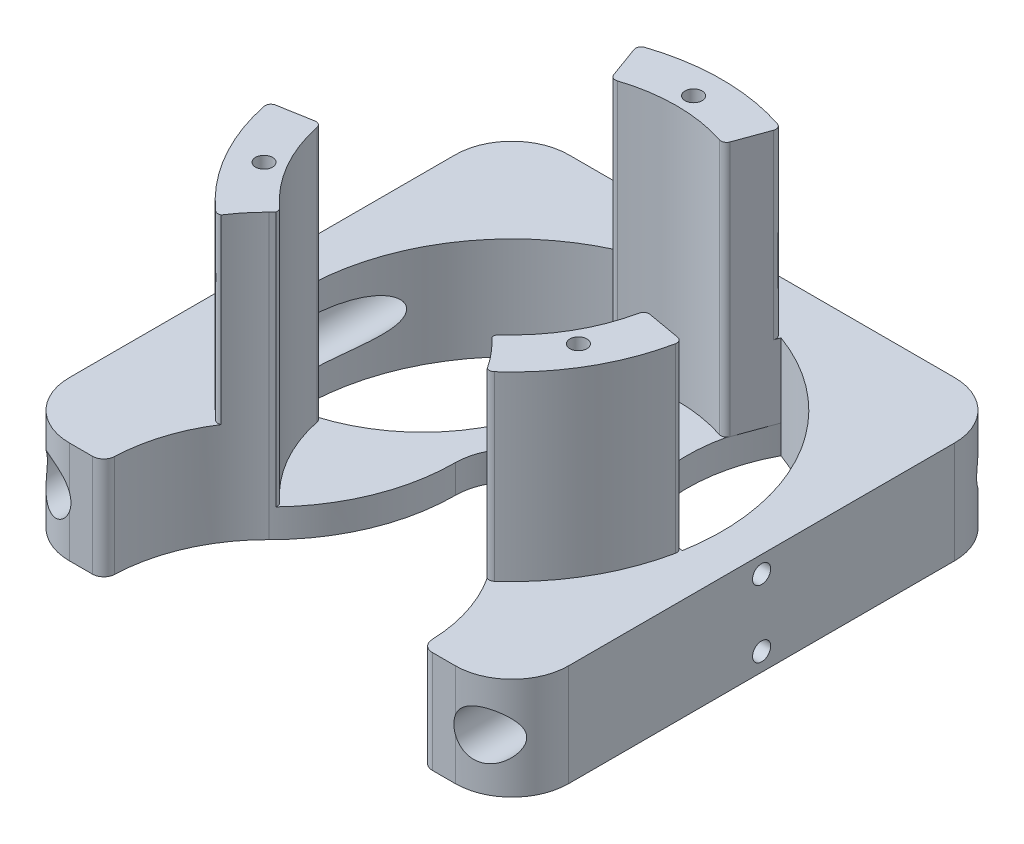
SolidWorks part; units mm, degrees
ref_plane "Front Plane" through (0, 0, 0) normal (0, 0, 1) x (1, 0, 0)
ref_plane "Top Plane" through (0, 0, 0) normal (0, 1, 0) x (1, 0, 0)
ref_plane "Right Plane" through (0, 0, 0) normal (1, 0, 0) x (0, 0, -1)
sketch "Sketch1" plane through (0, 0, 0) normal (0, 1, 0) x (1, 0, 0)
  line L0 (-44, 0) -> (-44, -44) construction
  line L1 (-44, -44) -> (44, -44) construction
  line L2 (44, -44) -> (44, 0) construction
  line L4 (-44, -44) -> (44, -44)
  line L5 (-44, -44) -> (-44, 44)
  line L6 (-44, 44) -> (44, 44)
  line L7 (44, -44) -> (44, 44)
  arc A0 (44, 0) -> (-44, 0) centre (0, 0) ccw construction
  dimension "D1" = 88
extrude "Boss-Extrude1" add sketch "Sketch1" along normal blind 18
sketch "Sketch2" plane through (0, 0, 44) normal (0, 0, 1) x (1, 0, 0)
  line L1 (-1044, 9) -> (48956, 9) construction
  line L2 (0, -1000) -> (0, 49000) construction
  line L3 (-44, 18) -> (-44, 0) construction
  circle A0 centre (-38, 9) radius 4.25
  circle A1 centre (38, 9) radius 4.25
  point P7 (-44, 9)
  dimension "D1" = 8.5
  dimension "D2" = 6
extrude "Cut-Extrude1" cut sketch "Sketch2" against normal through all
fillet "Fillet1" radius 10 4 edges at (44, 9, 44) (-44, 9, 44) (44, 9, -44) (-44, 9, -44)
sketch "Sketch3" plane through (0, 18, 0) normal (0, 1, 0) x (1, 0, 0)
  circle A0 centre (0, 0) radius 37
  dimension "D1" = 74
extrude "Cut-Extrude2" cut sketch "Sketch3" against normal through all
sketch "Sketch5" plane through (0, 0, 0) normal (0, 1, 0) x (1, 0, 0)
  circle A0 centre (0, 0) radius 40.5
  circle A1 centre (0, 0) radius 10
  dimension "D1" = 20
extrude "Boss-Extrude2" add sketch "Sketch5" along normal blind 5
sketch "Sketch6" plane through (0, 5, 0) normal (0, 1, 0) x (1, 0, 0)
  line L0 (-12.6547, 34.7686) -> (0, 0) construction
  line L1 (0, 0) -> (12.6547, 34.7686) construction
  line L2 (0, -1000) -> (0, 49000) construction
  line L3 (-12.6547, 34.7686) -> (-9.9186, 27.2511)
  line L4 (9.9186, 27.2511) -> (12.6547, 34.7686)
  arc A1 (-12.6547, 34.7686) -> (12.6547, 34.7686) centre (0, 0) cw
  arc A2 (-9.9186, 27.2511) -> (9.9186, 27.2511) centre (0, 0) cw
  circle A3 centre (0, 0) radius 37 construction
  dimension "D3" = 8
  dimension "D4" = 74
  dimension "D1" = 20
  dimension "D2" = 20
extrude "Boss-Extrude3" add sketch "Sketch6" along normal blind 45
sketch "Sketch7" plane through (0, 50, 0) normal (0, 1, 0) x (1, 0, 0)
  line L0 (0, 32) -> (0, 0) construction
  line L1 (0, -1000) -> (0, 49000) construction
  circle A0 centre (0, 32) radius 1.5
  dimension "D1" = 3
  dimension "D2" = 32
  dimension "D3" = 0
extrude "Cut-Extrude3" cut sketch "Sketch7" against normal through all
pattern_circular "CirPattern1" count 3 over 360 about axis through (0, 0, 0) along (0, 1, 0) of "Boss-Extrude3", "Cut-Extrude3"
sketch "Sketch10" plane through (0, 5, 0) normal (0, 1, 0) x (1, 0, 0)
  arc A0 (12.6547, 34.7686) -> (36.4379, -6.425) centre (37.307, 21.5392) ccw
  circle A1 centre (0, 0) radius 37 construction
  arc A2 (36.4379, -6.425) -> (12.6547, 34.7686) centre (0, 0) ccw
extrude "Cut-Extrude6" cut sketch "Sketch10" against normal through all
pattern_circular "CirPattern2" count 3 over 360 about axis through (0, 0, 0) along (0, 1, 0) of "Cut-Extrude6"
fillet "Fillet4" radius 1 12 edges at (-18.6408, 27.5, 22.2153) (-28.5594, 27.5, 5.0358) (-36.4379, 34, 6.425) (-23.7831, 34, 28.3436) (23.7831, 34, 28.3436) (18.6408, 27.5, 22.2153) (36.4379, 34, 6.425) (28.5594, 27.5, 5.0358) (12.6547, 34, -34.7686) (-12.6547, 34, -34.7686) (9.9186, 27.5, -27.2511) (-9.9186, 27.5, -27.2511)
sketch "Sketch12" plane through (0, 0, 0) normal (0, 1, 0) x (1, 0, 0)
  circle A0 centre (0, -43.0784) radius 27.9777
  arc A1 (23.7831, -28.3436) -> (-23.7831, -28.3436) centre (0, -43.0784) ccw construction
extrude "Cut-Extrude8" cut sketch "Sketch12" along normal through all
sketch "Sketch13" plane through (0, 0, 0) normal (0, 1, 0) x (1, 0, 0)
  arc A0 (-10, 0) -> (10, 0) centre (0, 0) ccw
  arc A4 (-19.678, -23.1905) -> (19.678, -23.1905) centre (0, -43.0784) cw
  arc A7 (-10, 0) -> (-19.678, -23.1905) centre (-42.6237, 0) cw
  arc A8 (10, 0) -> (19.678, -23.1905) centre (42.6237, 0) ccw
  circle A9 centre (0, 0) radius 10 construction
  arc A10 (19.0829, -22.6188) -> (-19.0829, -22.6188) centre (0, -43.0784) ccw construction
extrude "Cut-Extrude9" cut sketch "Sketch13" along normal through all
sketch "Sketch14" plane through (0, 0, -44) normal (0, 0, -1) x (-1, 0, 0)
  circle A0 centre (-38, 9) radius 4.25
  circle A1 centre (38, 9) radius 4.25
  arc A2 (34, 10.4361) -> (34, 7.5639) centre (38, 9) ccw construction
  arc A3 (-34, 7.5639) -> (-34, 10.4361) centre (-38, 9) ccw construction
extrude "Cut-Extrude10" cut sketch "Sketch14" against normal through all
fillet "Fillet5" radius 2 2 edges at (27.9625, 9, 44) (-27.9625, 9, 44)
sketch "Sketch15" plane through (44, 0, 0) normal (1, 0, 0) x (0, 0, -1)
  line L0 (-34, 18) -> (34, 18) construction
  line L1 (-34, 0) -> (34, 0) construction
  circle A0 centre (0, 15) radius 1.6
  circle A1 centre (0, 3.2) radius 1.6
  dimension "D1" = 3.2
  dimension "D2" = 3
  dimension "D3" = 3.2
extrude "Cut-Extrude11" cut sketch "Sketch15" against normal up to next
mirror "Mirror1" about plane through (0, 0, 0) normal (1, 0, 0) of "Cut-Extrude11"
